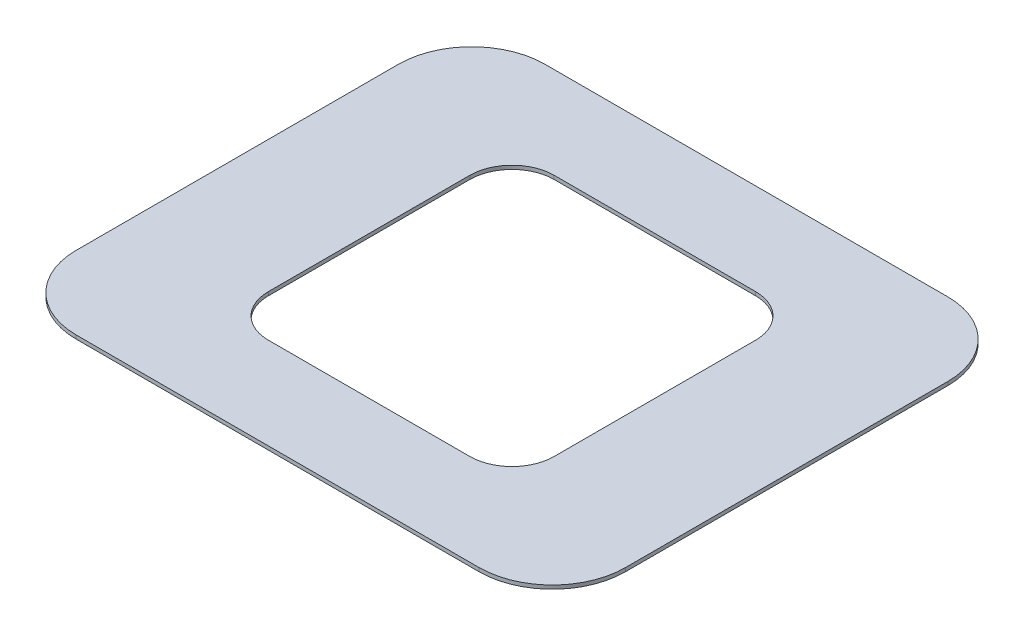
SolidWorks part; units mm, degrees
ref_plane "Front Plane" through (0, 0, 0) normal (0, 0, 1) x (1, 0, 0)
ref_plane "Top Plane" through (0, 0, 0) normal (0, 1, 0) x (1, 0, 0)
ref_plane "Right Plane" through (0, 0, 0) normal (1, 0, 0) x (0, 0, -1)
sketch "Sketch1" plane through (0, 0, 0) normal (0, 1, 0) x (1, 0, 0)
  line L1 (-92.717, 79.5943) -> (127.283, 79.5943)
  line L2 (-132.717, 39.5943) -> (-132.717, -136.4057)
  line L3 (-92.717, -176.4057) -> (127.283, -176.4057)
  line L4 (167.283, 39.5943) -> (167.283, -136.4057)
  line L5 (-37.717, 29.5943) -> (72.283, 29.5943)
  line L6 (-60.717, 6.5943) -> (-60.717, -103.4057)
  line L7 (-37.717, -126.4057) -> (72.283, -126.4057)
  line L8 (95.283, 6.5943) -> (95.283, -103.4057)
  arc A0 (127.283, 79.5943) -> (167.283, 39.5943) centre (127.283, 39.5943) cw
  arc A1 (127.283, -176.4057) -> (167.283, -136.4057) centre (127.283, -136.4057) ccw
  arc A2 (-132.717, -136.4057) -> (-92.717, -176.4057) centre (-92.717, -136.4057) ccw
  arc A3 (-132.717, 39.5943) -> (-92.717, 79.5943) centre (-92.717, 39.5943) cw
  arc A4 (-60.717, -103.4057) -> (-37.717, -126.4057) centre (-37.717, -103.4057) ccw
  arc A5 (72.283, -126.4057) -> (95.283, -103.4057) centre (72.283, -103.4057) ccw
  arc A6 (72.283, 29.5943) -> (95.283, 6.5943) centre (72.283, 6.5943) cw
  arc A7 (-37.717, 29.5943) -> (-60.717, 6.5943) centre (-37.717, 6.5943) ccw
  point P6 (167.283, 79.5943)
  point P9 (167.283, -176.4057)
  point P14 (-132.717, 79.5943)
  point P21 (-60.717, -126.4057)
  point P26 (95.283, 29.5943)
  point P29 (-60.717, 29.5943)
  dimension "D3" = 40
  dimension "D6" = 23
  dimension "D1" = 300
  dimension "D2" = 256
  dimension "D4" = 156
  dimension "D5" = 156
  dimension "D7" = 50
  dimension "D8" = 72
extrude "Boss-Extrude1" add sketch "Sketch1" along normal blind 2
equation "\"D7@Sketch1\"=(\"D2@Sketch1\"-\"D5@Sketch1\")/2"
equation "\"D8@Sketch1\"=(\"D1@Sketch1\"-\"D4@Sketch1\")/2"
